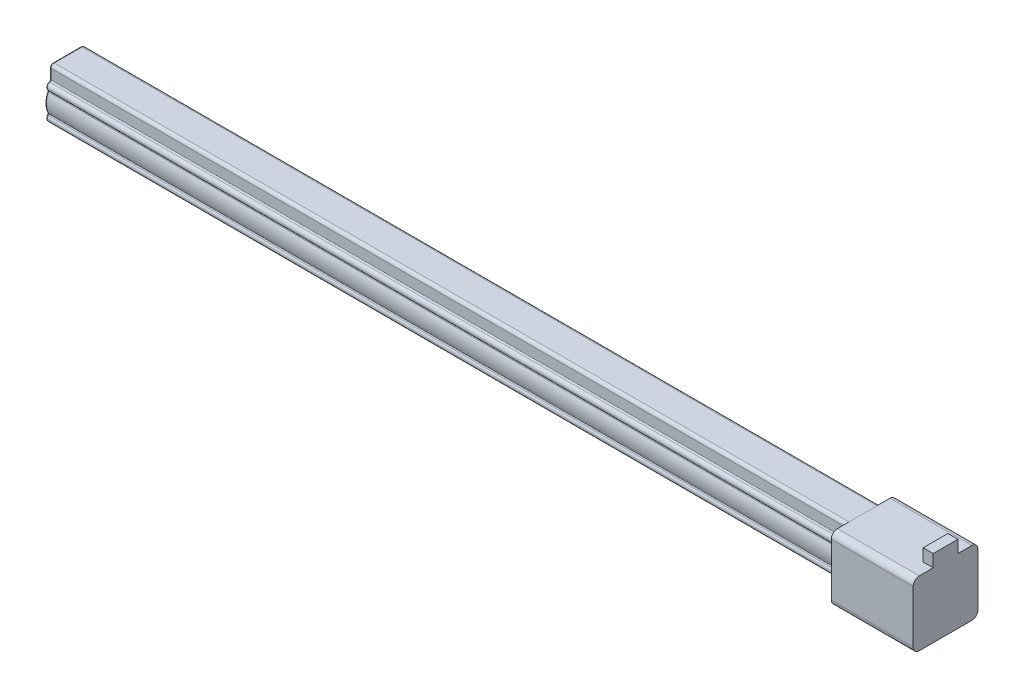
SolidWorks part; units mm, degrees
ref_plane "Спереди" through (0, 0, 0) normal (0, 0, 1) x (1, 0, 0)
ref_plane "Сверху" through (0, 0, 0) normal (0, 1, 0) x (1, 0, 0)
ref_plane "Справа" through (0, 0, 0) normal (1, 0, 0) x (0, 0, -1)
sketch "Эскиз1" plane through (0, 0, 0) normal (0, 0, 1) x (1, 0, 0)
  line L0 (-29, 21) -> (-545, 21)
  line L1 (24, -21) -> (-24, -21)
  line L2 (24, -21) -> (24, 21)
  line L3 (24, 21) -> (-24, 21)
  line L4 (-24, -21) -> (-24, 21)
  line L5 (24, -21) -> (-24, 21) construction
  line L6 (24, 21) -> (-24, -21) construction
  line L7 (-24, -21) -> (-29, -21)
  line L8 (-24, -21) -> (-24, 21)
  line L9 (-24, 21) -> (-29, 21)
  line L10 (-29, -21) -> (-29, 21)
  line L11 (-545, 21) -> (-545, -14)
  line L12 (-545, -14) -> (-29, -14)
  point P0 (0, 0)
  dimension "D1" = 48
  dimension "D2" = 42
  dimension "D3" = 5
  dimension "D4" = 516
  dimension "D5" = 35
extrude "Бобышка-Вытянуть1" add sketch "Эскиз1" along normal blind 42 contours L11 L12 L10 L0 | L10 L7 L4 L9 | L4 L1 L2 L3 region at (-287, 3.5, 0) region at (-26.5, 0, 0) region at (0, 0, 0)
sketch "Эскиз2" plane through (0, 0, 42) normal (0, 0, 1) x (1, 0, 0)
  line L0 (-29, -14) -> (-29, 21)
  line L1 (24, 21) -> (-545, 21) construction
split line "Разделяющая линия1"
sketch "Эскиз3" plane through (0, 21, 0) normal (0, 1, 0) x (1, 0, 0)
  line L1 (-545, 0) -> (-29, 0)
  line L2 (-545, 0) -> (-545, -42)
  line L3 (-545, -42) -> (-29, -42)
  line L4 (-29, 0) -> (-29, -42)
extrude "Вырез-Вытянуть1" cut sketch "Эскиз3" against normal blind 0.5
fillet "Скругление1" radius 7 4 edges at (-287, -14, 0) (-287, 20.5, 0) (-287, -14, 42) (-287, 20.5, 42)
sketch "Эскиз4" plane through (-545, 0, 0) normal (-1, 0, 0) x (0, 0, 1)
  line L0 (21, 21) -> (21, -21) construction
  line L1 (42, 21) -> (0, 21) construction
  line L2 (42, -21) -> (0, -21) construction
  circle A0 centre (21, 0) radius 10
  dimension "D1" = 20
extrude "Вырез-Вытянуть2" cut sketch "Эскиз4" against normal up to surface (516 mm away) up to face at (-29, -14.4832, 21)
sketch "Эскиз5" plane through (-545, 0, 0) normal (-1, 0, 0) x (0, 0, 1)
  line L1 (32, 7.5) -> (10, 7.5)
  line L2 (32, 7.5) -> (32, 20.5)
  line L3 (32, 20.5) -> (10, 20.5)
  line L4 (0, 13.5) -> (0, -7)
  line L5 (7, -14) -> (35, -14)
  line L6 (42, -7) -> (42, 13.5)
  line L7 (35, 20.5) -> (7, 20.5)
  line L8 (0, 13.5) -> (0, -7)
  line L9 (7, -14) -> (35, -14)
  line L10 (42, -7) -> (42, 13.5)
  line L11 (35, 20.5) -> (7, 20.5)
  line L12 (10, 7.5) -> (10, 20.5)
  line L13 (32, 7.5) -> (10, 20.5) construction
  line L14 (32, 20.5) -> (10, 7.5) construction
  line L15 (32, -8.6603) -> (10, -8.6603)
  line L16 (32, -8.6603) -> (32, 8.6603)
  line L17 (32, 8.6603) -> (10, 8.6603)
  line L18 (10, -8.6603) -> (10, 8.6603)
  line L19 (32, -8.6603) -> (10, 8.6603) construction
  line L20 (32, 8.6603) -> (10, -8.6603) construction
  circle A0 centre (21, 0) radius 14
  circle A1 centre (10, 8.6603) radius 2.5
  circle A2 centre (10, -8.6603) radius 2.5
  circle A3 centre (32, -8.6603) radius 2.5
  circle A4 centre (32, 8.6603) radius 2.5
  arc A5 (0, -7) -> (7, -14) centre (7, -7) ccw
  arc A6 (35, -14) -> (42, -7) centre (35, -7) ccw
  arc A7 (42, 13.5) -> (35, 20.5) centre (35, 13.5) ccw
  arc A8 (7, 20.5) -> (0, 13.5) centre (7, 13.5) ccw
  arc A9 (0, -7) -> (7, -14) centre (7, -7) ccw
  arc A10 (35, -14) -> (42, -7) centre (35, -7) ccw
  arc A11 (42, 13.5) -> (35, 20.5) centre (35, 13.5) ccw
  arc A12 (7, 20.5) -> (0, 13.5) centre (7, 13.5) ccw
  point P5 (21, 14)
  line M11 (0, 13.5) -> (0, -7)
  arc M12 (0, -7) -> (7, -14) centre (7, -7) ccw
  line M13 (7, -14) -> (35, -14)
  arc M14 (35, -14) -> (42, -7) centre (35, -7) ccw
  line M15 (42, -7) -> (42, 13.5)
  arc M16 (42, 13.5) -> (35, 20.5) centre (35, 13.5) ccw
  line M17 (35, 20.5) -> (7, 20.5)
  arc M18 (7, 20.5) -> (0, 13.5) centre (7, 13.5) ccw
  dimension "D3" = 5
  dimension "D2" = 22
  dimension "D1" = 0
extrude "Вырез-Вытянуть3" cut sketch "Эскиз5" against normal up to surface (516 mm away) contours A0 L12 M17 M18 M11 M12 M13 | A0 L9 L2 M14 M15 M16 M17 region at (-545, 2.964, 36.9969) region at (-545, 2.964, 5.0031) up to face at (-29, 18.8166, 21)
fillet "Скругление2" radius 2 2 edges at (-287, 20.5, 10) (-287, 20.5, 32)
fillet "Скругление3" radius 4 4 edges at (-2.5, -21, 0) (-2.5, -21, 42) (-2.5, 21, 0) (-2.5, 21, 42)
fillet "Скругление5" radius 1 20 edges at (-545, 9.3722, 7.6035) (-545, -10.2067, 8.0357) (-545, -10.2067, 33.9643) (-545, 9.3722, 34.3965) (-545, 14.8301, 32) (-545, 19.9142, 31.4142) (-545, 20.5, 21) (-545, 19.9142, 10.5858) (-287, 11.1603, 10) (-287, 6.5657, 8.6351) (-287, -6.5657, 8.6351) (-287, -10.4786, 11.7157) (-287, -10.4786, 30.2843) (-287, -6.5657, 33.3649) (-287, 6.5657, 33.3649) (-287, 11.1603, 32) (-545, -14, 21) (-545, 0, 7) (-545, 0, 35) (-545, 14.8301, 10)
sketch "Эскиз6" plane through (0, 21, 0) normal (0, 1, 0) x (1, 0, 0)
  line L0 (24, -38) -> (24, -4) construction
  line L1 (30.5, -29) -> (17.5, -29)
  line L2 (30.5, -29) -> (30.5, -13)
  line L3 (30.5, -13) -> (17.5, -13)
  line L4 (17.5, -29) -> (17.5, -13)
  line L5 (30.5, -29) -> (17.5, -13) construction
  line L6 (30.5, -13) -> (17.5, -29) construction
  point P0 (24, -21)
  line M3 (24, -38) -> (24, -4)
  dimension "D1" = 13
  dimension "D2" = 16
extrude "Бобышка-Вытянуть2" add sketch "Эскиз6" along normal blind 8 contours L4 L1 L3 M3 region at (20.75, 21, 21)
